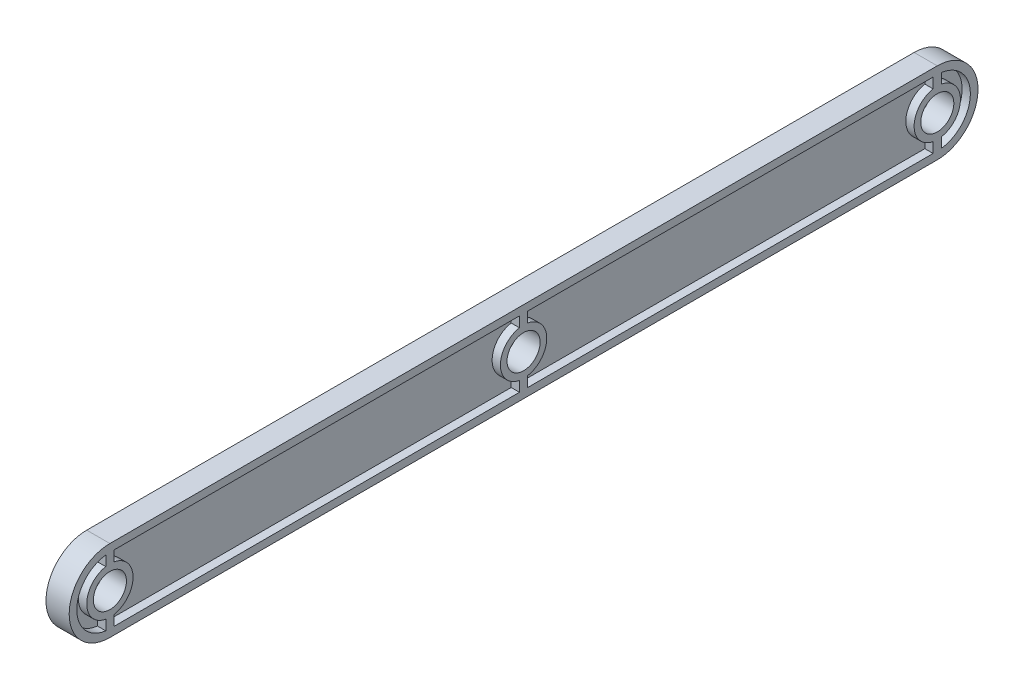
SolidWorks part; units mm, degrees
note: The reader was unsure of these and kept them because the rebuilt part matched: shared geometry of "Sketch1<3>".
material "Cast Alloy Steel"
ref_plane "Front Plane" through (0, 0, 0) normal (0, 0, 1) x (1, 0, 0)
ref_plane "Top Plane" through (0, 0, 0) normal (0, 1, 0) x (1, 0, 0)
ref_plane "Right Plane" through (0, 0, 0) normal (1, 0, 0) x (0, 0, -1)
sketch "Sketch1" plane through (0, 0, 0) normal (1, 0, 0) x (0, 0, -1)
  line L0 (-48.8786, 0) -> (451.1214, 0) construction
  line L2 (-48.8786, 24.6078) -> (451.1214, 24.6078)
  line L3 (-48.8786, -24.6078) -> (451.1214, -24.6078)
  arc A0 (-48.8786, 24.6078) -> (-48.8786, -24.6078) centre (-48.8786, 0) ccw
  arc A1 (451.1214, -24.6078) -> (451.1214, 24.6078) centre (451.1214, 0) ccw
  circle A2 centre (-48.8786, 0) radius 10
  circle A3 centre (451.1214, 0) radius 10
  circle A4 centre (201.1214, 0) radius 10
  point P5 (201.1214, 0)
  dimension "D1" = 20
  dimension "D2" = 20
  dimension "D3" = 20
extrude "Boss-Extrude1" add sketch "Sketch1" along normal mid plane 4
sketch "草图1" plane through (2, 0, 0) normal (1, 0, 0) x (0, 0, -1)
  line L0 (-48.8786, 0) -> (451.1214, 0) construction
  line L1 (-48.8786, 24.6078) -> (451.1214, 24.6078)
  line L2 (-48.8786, -24.6078) -> (451.1214, -24.6078)
  arc A0 (-48.8786, 24.6078) -> (-48.8786, -24.6078) centre (-48.8786, 0) ccw
  arc A1 (451.1214, -24.6078) -> (451.1214, 24.6078) centre (451.1214, 0) ccw
  circle A2 centre (-48.8786, 0) radius 10
  circle A3 centre (451.1214, 0) radius 10
  circle A4 centre (201.1214, 0) radius 10
  point P4 (201.1214, 0)
extrude "凸台-拉伸1" add sketch "草图1" along normal blind 5
sketch "草图2" plane through (-2, 0, 0) normal (-1, 0, 0) x (0, 0, 1)
  line L0 (-451.1214, 0) -> (48.8786, 0) construction
  line L1 (-451.1214, 24.6078) -> (48.8786, 24.6078)
  line L2 (-451.1214, -24.6078) -> (48.8786, -24.6078)
  arc A0 (-451.1214, 24.6078) -> (-451.1214, -24.6078) centre (-451.1214, 0) ccw
  arc A1 (48.8786, -24.6078) -> (48.8786, 24.6078) centre (48.8786, 0) ccw
  point P4 (-201.1214, 0)
extrude "凸台-拉伸2" add sketch "草图2" along normal blind 5
sketch "草图4" plane through (-7, 0, 0) normal (-1, 0, 0) x (0, 0, 1)
  line L5 (-451.1214, 20) -> (48.8786, 20)
  line L6 (-451.1214, -20) -> (48.8786, -20)
  circle A0 centre (-451.1214, 0) radius 14
  circle A1 centre (-201.1214, 0) radius 14.0002
  circle A2 centre (-451.1214, 0) radius 10
  circle A3 centre (48.8786, 0) radius 10
  circle A4 centre (-201.1214, 0) radius 10
  arc A5 (-451.1214, 20) -> (-451.1214, -20) centre (-451.1214, 0) ccw
  arc A6 (48.8786, 20) -> (48.8786, -20) centre (48.8786, 0) cw
  circle A7 centre (48.8786, 0) radius 14
extrude "切除-拉伸1" cut sketch "草图4" against normal blind 5 contours A6 L5 A5 L6 A7 A1 A0
ref_plane "基准面1" through (0, 0, 0) normal (-1, 0, 0) x (0, 0, 1)
mirror "镜向1" about plane through (0, 0, 0) normal (-1, 0, 0) of "切除-拉伸1"
extrude "切除-拉伸2" cut sketch "Sketch1<3>" against normal mid plane 30
sketch "Sketch1<3>" plane through (0, 0, 0) normal (1, 0, 0) x (0, 0, -1) same geometry as "Sketch1"
sketch "草图5" plane through (-7, 0, 0) normal (-1, 0, 0) x (0, 0, 1)
  line L0 (48.8786, 14) -> (48.8786, 20)
  line L1 (48.8786, -14) -> (48.8786, -20)
  line L2 (-201.1214, -14.0002) -> (-201.1214, -20)
  line L3 (-201.1214, 14.0002) -> (-201.1214, 20)
  line L4 (-451.1214, 14) -> (-451.1214, 20)
  line L5 (-451.1214, -14) -> (-451.1214, -20)
rib "筋2" sketch "草图5" sketch "草图5" thickness 5 extrusion direction normal to sketch draft on no parameters "D1"=5
mirror "镜向2" about plane through (0, 0, 0) normal (-1, 0, 0) of "筋2"
